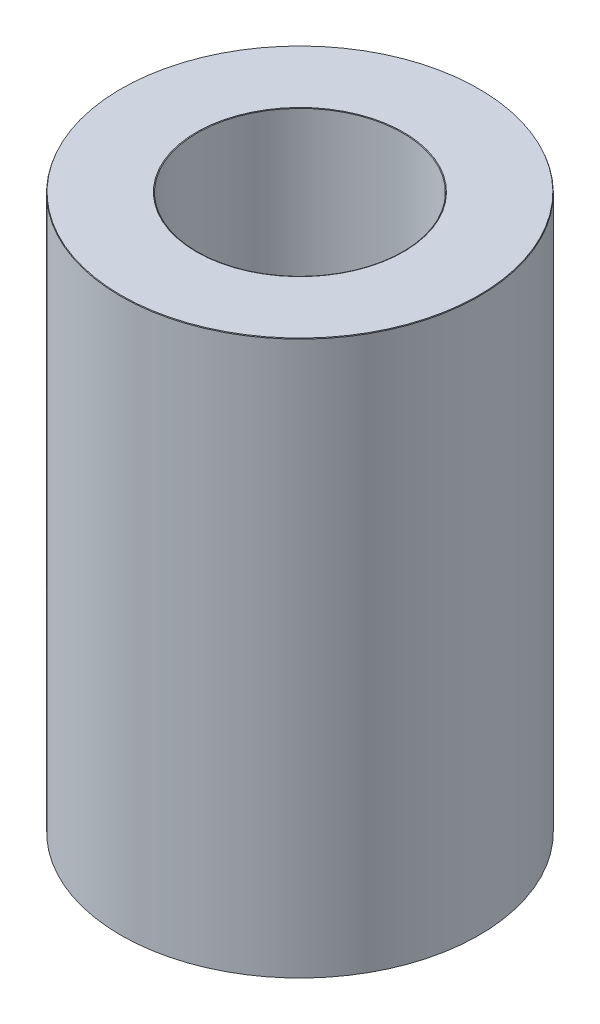
SolidWorks part; units mm, degrees
ref_plane "Front Plane" through (0, 0, 0) normal (0, 0, 1) x (1, 0, 0)
ref_plane "Top Plane" through (0, 0, 0) normal (0, 1, 0) x (1, 0, 0)
ref_plane "Right Plane" through (0, 0, 0) normal (1, 0, 0) x (0, 0, -1)
sketch "Sketch1" plane through (0, 0, 0) normal (0, 1, 0) x (1, 0, 0)
  circle A0 centre (0, 0) radius 55
  dimension "SLEEVE_OD" = 110
extrude "Boss-Extrude1" add sketch "Sketch1" along normal blind 170.1621
sketch "Sketch2" plane through (0, 0, 0) normal (0, 1, 0) x (1, 0, 0)
  circle A0 centre (0, 0) radius 31.5803
  dimension "BORE_D" = 63.1606
extrude "Cut-Extrude1" cut sketch "Sketch2" along normal through all
chamfer "Chamfer1" distance 0.2278 angle 23.314 4 edges at (0, 170.1621, 31.5803) (0, 0, 31.5803) (0, 0, 55) (0, 170.1621, 55) first distance on face at (0, 170.1621, 31.5803) first distance on face at (0, 0, 31.5803) first distance on face at (0, 170.1621, 55)
